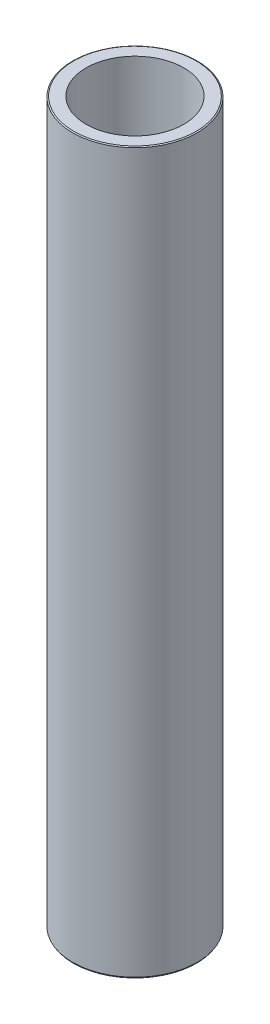
SolidWorks part; units mm, degrees
ref_plane "Front Plane" through (0, 0, 0) normal (0, 0, 1) x (1, 0, 0)
ref_plane "Top Plane" through (0, 0, 0) normal (0, 1, 0) x (1, 0, 0)
ref_plane "Right Plane" through (0, 0, 0) normal (1, 0, 0) x (0, 0, -1)
sketch "Sketch1" plane through (0, 0, 0) normal (0, 1, 0) x (1, 0, 0)
  circle A0 centre (0, 0) radius 42.5
  dimension "SHAFT_OD" = 85
extrude "Boss-Extrude1" add sketch "Sketch1" along normal blind 491.3464
sketch "Sketch2" plane through (0, 0, 0) normal (0, 1, 0) x (1, 0, 0)
  circle A0 centre (0, 0) radius 33.3692
  dimension "BORE_D" = 66.7384
extrude "Cut-Extrude1" cut sketch "Sketch2" along normal through all
chamfer "Chamfer1" distance 0.462 angle 60 2 edges at (0, 491.3464, 42.5) (0, 0, 42.5) first distance on face at (0, 491.3464, 42.5) first distance on face at (0, 0, 33.3692)
